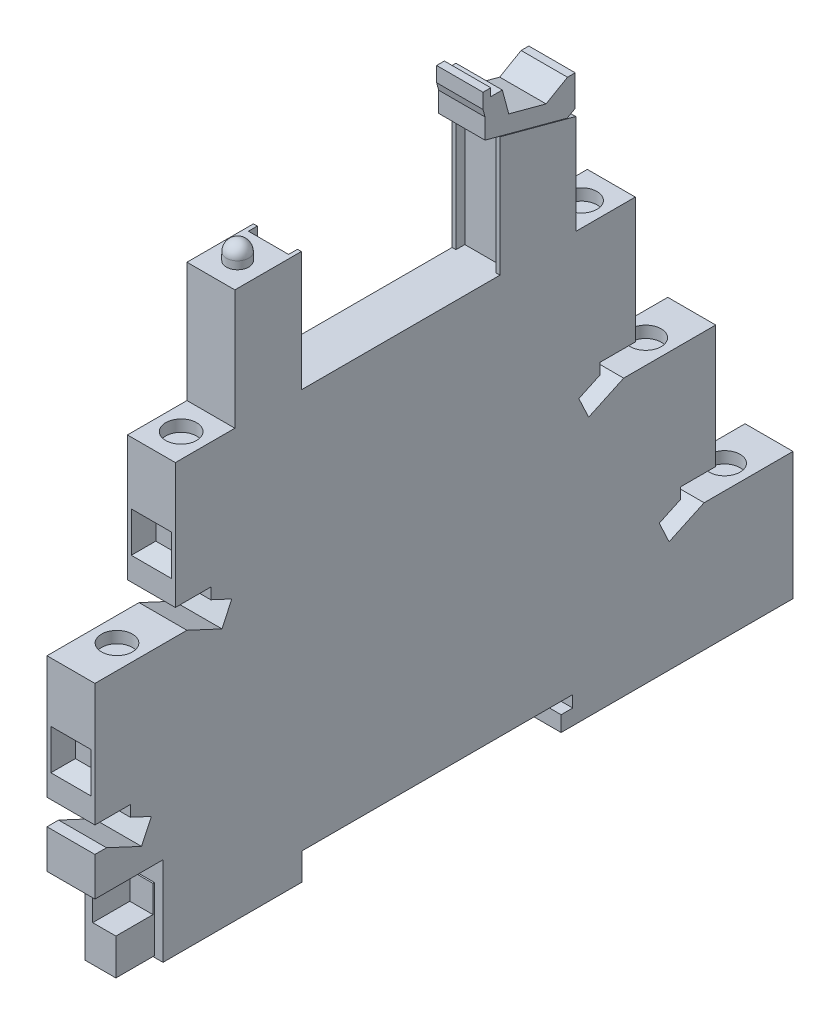
SolidWorks part; units mm, degrees
material "PVC Rigid"
ref_plane "Piano frontale" through (0, 0, 0) normal (0, 0, 1) x (1, 0, 0)
ref_plane "Piano superiore" through (0, 0, 0) normal (0, 1, 0) x (1, 0, 0)
ref_plane "Piano destro" through (0, 0, 0) normal (1, 0, 0) x (0, 0, -1)
sketch "Sketch1" plane through (0, 0, 0) normal (1, 0, 0) x (0, 0, -1)
  line L0 (0, 0) -> (0, 3.5)
  line L1 (0, 3.5) -> (35, 3.5)
  line L2 (35, 3.5) -> (35, 2)
  line L3 (35, 2) -> (33.5, 2)
  line L4 (33.5, 2) -> (33.5, 0)
  line L5 (33.5, 0) -> (63.5, 0)
  line L6 (63.5, 0) -> (63.5, 16.5)
  line L7 (63.5, 16.5) -> (52, 16.5)
  line L8 (52, 16.5) -> (47.4685, 14.3869)
  line L9 (47.4685, 14.3869) -> (46.2006, 17.1058)
  line L10 (46.2006, 17.1058) -> (48.9195, 18.3737)
  line L11 (48.9195, 18.3737) -> (48.9195, 19.8)
  line L12 (48.9195, 19.8) -> (53.5, 19.8)
  line L13 (53.5, 35.6631) -> (53.5, 19.8)
  line L14 (38.5138, 38.9631) -> (43.0943, 38.9631)
  line L15 (41.5943, 35.6631) -> (37.0627, 33.55)
  line L16 (43.0943, 55.2) -> (43.0943, 38.9631)
  line L17 (38.5138, 37.5368) -> (38.5138, 38.9631)
  line L18 (35.7949, 36.2689) -> (38.5138, 37.5368)
  line L19 (53.5, 35.6631) -> (41.5943, 35.6631)
  line L20 (37.0627, 33.55) -> (35.7949, 36.2689)
  line L21 (43.0943, 55.2) -> (35.3943, 55.2)
  line L22 (35.3943, 55.2) -> (35.3943, 68.0741)
  line L24 (25.5943, 70.7) -> (25.5943, 55.2)
  line L25 (25.5943, 55.2) -> (-0.1057, 55.2)
  line L26 (-0.1057, 55.2) -> (-0.1057, 70.7)
  line L27 (-0.1057, 70.7) -> (-8.7057, 70.7)
  line L28 (-8.7057, 70.7) -> (-8.7057, 55.2)
  line L29 (-8.7057, 55.2) -> (-16.4057, 55.2)
  line L30 (-16.4057, 55.2) -> (-16.4057, 38.9631)
  line L31 (-26.8114, 16.5) -> (-25.3114, 16.5)
  line L32 (13.3443, 46.9131) -> (13.3443, 20.627) construction
  line L33 (-22.231, 19.8) -> (-26.8114, 19.8)
  line L34 (-22.231, 18.3737) -> (-22.231, 19.8)
  line L35 (-19.512, 17.1058) -> (-22.231, 18.3737)
  line L36 (-20.7799, 14.3869) -> (-19.512, 17.1058)
  line L37 (-25.3114, 16.5) -> (-20.7799, 14.3869)
  line L38 (-26.8114, 35.6631) -> (-26.8114, 19.8)
  line L39 (-26.8114, 35.6631) -> (-14.9057, 35.6631)
  line L40 (-10.3742, 33.55) -> (-9.1063, 36.2689)
  line L41 (-9.1063, 36.2689) -> (-11.8252, 37.5368)
  line L42 (-11.8252, 37.5368) -> (-11.8252, 38.9631)
  line L43 (-14.9057, 35.6631) -> (-10.3742, 33.55)
  line L44 (-11.8252, 38.9631) -> (-16.4057, 38.9631)
  line L45 (-26.8114, 16.5) -> (-26.8114, 11.5)
  line L46 (0, 0) -> (-18, 0)
  line L47 (-18, 0) -> (-18, 11.5)
  line L48 (-18, 11.5) -> (-26.8114, 11.5)
  line L49 (25.5943, 70.7) -> (35.3943, 68.0741)
  dimension "D1" = 3.5
  dimension "D2" = 35
  dimension "D3" = 1.5
  dimension "D4" = 1.5
  dimension "D5" = 30
  dimension "D6" = 16.5
  dimension "D7" = 11.5
  dimension "D8" = 5
  dimension "D9" = 25
  dimension "D10" = 3
  dimension "D11" = 3
  dimension "D12" = 3.3
  dimension "D13" = 10
  dimension "D14" = 7.7
  dimension "D17" = 25.7
  dimension "D18" = 8.6
  dimension "D19" = 7.7
  dimension "D20" = 5
  dimension "D21" = 18
  dimension "D22" = 19.1631
  dimension "D23" = 51.7
  dimension "D24" = 55.2
extrude "Boss-Extrude1" add sketch "Sketch1" along normal blind 6.2 contours L25 L26 L27 L28 L29 L30 L44 L42 L41 L40 L43 L39 L38 L33 L34 L35 L36 L37 L31 L45 L48 L47 L46 L0 L1 L2 L3 L4 L5 L6 L7 L8 L9 L10 L11 L12 L13 L19 L15 L20 L18 L17 L14 L16 L21 L22 L49 L24
sketch "Sketch2" plane through (0, 70.7, 0) normal (0, 1, 0) x (1, 0, 0)
  line L0 (0, -0.1057) -> (0, -8.7057) construction
  line L1 (0.5, -1.2557) -> (5.7, -1.2557)
  line L2 (0.5, -1.2557) -> (0.5, 26.7443)
  line L3 (0.5, 26.7443) -> (5.7, 26.7443)
  line L4 (5.7, -1.2557) -> (5.7, 26.7443)
  line L5 (6.2, 25.5943) -> (6.2, -0.1057) construction
  line L6 (6.2, -0.1057) -> (0, -0.1057) construction
  dimension "D1" = 28
  dimension "D2" = 5.2
  dimension "D3" = 0.5
  dimension "D4" = 0.5
  dimension "D5" = 1.15
extrude "Cut-Extrude1" cut sketch "Sketch2" against normal up to vertex (15.5 mm away) up to point (0, 55.2, 0.1057)
sketch "Sketch3" plane through (0, 70.7, 0) normal (0, 1, 0) x (1, 0, 0)
  line L0 (0.5, -1.2557) -> (5.7, -1.2557) construction
  line L1 (6.2, -8.7057) -> (0, -8.7057) construction
  circle A0 centre (3.1, -5.2557) radius 1.45
  dimension "D1" = 2.9
  dimension "D3" = 3.45
  dimension "D2" = 4
extrude "Boss-Extrude2" add sketch "Sketch3" along normal blind 1 contours A0
dome "Dome1" faces to dome 1 distance 1.45 reverse direction no elliptical dome no face at (3.1, 71.7, 6.7057) parameters "D1"=1.45
sketch "Sketch4" plane through (0, 0, 18) normal (0, 0, 1) x (1, 0, 0)
  line L2 (1.1, 0.2) -> (1.1, 8.4)
  line L3 (1.1, 8.4) -> (5.1, 8.4)
  line L4 (5.1, 0.2) -> (5.1, 8.4)
  line L5 (6.2, 0) -> (6.2, 11.5) construction
  line L6 (1.1, 0.2) -> (5.1, 0.2)
  line L7 (6.2, 0) -> (0, 0) construction
  dimension "D1" = 8.2
  dimension "D2" = 8.4
  dimension "D3" = 1.1
extrude "Boss-Extrude3" add sketch "Sketch4" along normal blind 5
sketch "Sketch5" plane through (0, 0, 23) normal (0, 0, 1) x (1, 0, 0)
  line L1 (5.1, 8.4) -> (2.1, 8.4)
  line L2 (5.1, 8.4) -> (5.1, 4.9)
  line L3 (5.1, 4.9) -> (2.1, 4.9)
  line L4 (2.1, 8.4) -> (2.1, 4.9)
  dimension "D1" = 3.5
  dimension "D2" = 3
extrude "Cut-Extrude2" cut sketch "Sketch5" against normal blind 4.8
sketch "Sketch6" plane through (0, 0, 0) normal (0, 0, -1) x (-1, 0, 0)
  line L0 (-6.2, 0) -> (0, 0) construction
  line L1 (-5.1, 0) -> (-1.1, 0)
  line L2 (-5.1, 0) -> (-5.1, 2)
  line L3 (-5.1, 2) -> (-1.1, 2)
  line L4 (-1.1, 0) -> (-1.1, 2)
  line L5 (-6.2, 0) -> (-6.2, 3.5) construction
  dimension "D1" = 2
  dimension "D2" = 4
  dimension "D3" = 1.1
extrude "Boss-Extrude4" add sketch "Sketch6" along normal blind 1.5 draft 15
ref_plane "Plane1" through (3.1, 0, 0) normal (1, 0, 0) x (0, 0, -1)
sketch "Sketch7" plane through (3.1, 0, 0) normal (1, 0, 0) x (0, 0, -1)
  line L0 (34.3805, 68.3457) -> (23.7553, 71.1928)
  line L1 (25.5943, 70.7) -> (35.3943, 68.0741) construction
  line L2 (23.7553, 71.1928) -> (23.7553, 73.7928)
  line L3 (23.7553, 73.7928) -> (23.4965, 74.7587)
  line L4 (23.4965, 74.7587) -> (23.4965, 76.6928)
  line L5 (23.4965, 76.6928) -> (24.4965, 76.6928)
  line L6 (24.4965, 76.6928) -> (24.4965, 75.6928)
  line L7 (24.4965, 75.6928) -> (25.9965, 75.6928)
  line L8 (25.9965, 75.6928) -> (26.8247, 72.6018)
  line L9 (26.8247, 72.6018) -> (31.6543, 71.3077)
  line L10 (31.6543, 71.3077) -> (34.4256, 72.9077)
  line L11 (34.4256, 72.9077) -> (35.4256, 72.9077)
  line L12 (35.4256, 72.9077) -> (35.4256, 68.9077)
  line L13 (35.4256, 68.9077) -> (34.3805, 68.3457)
  dimension "D1" = 11
  dimension "D2" = 2.6
  dimension "D3" = 1
  dimension "D4" = 15
  dimension "D5" = 1
  dimension "D6" = 1
  dimension "D7" = 5.5
  dimension "D8" = 1
  dimension "D9" = 1.5
  dimension "D10" = 3.2
  dimension "D11" = 75
  dimension "D12" = 5
  dimension "D13" = 3.2
  dimension "D14" = 45
  dimension "D15" = 1
  dimension "D16" = 4
extrude "Boss-Extrude5" add sketch "Sketch7" along normal blind 3 and the other way blind 3
sketch "Sketch8" plane through (0, 55.2, 0) normal (0, 1, 0) x (1, 0, 0)
  line L0 (3.1, -42.181) -> (3.1, 42.181) construction
  circle A0 centre (3.1, 39.2443) radius 2
  circle A1 centre (3.1, -12.5557) radius 2
  dimension "D1" = 4
  dimension "D2" = 4
extrude "Cut-Extrude3" cut sketch "Sketch8" against normal blind 1.5
sketch "Sketch9" plane through (0, 35.6631, 0) normal (0, 1, 0) x (1, 0, 0)
  circle A0 centre (3.1, 47.5471) radius 2
  circle A1 centre (3.1, -20.8586) radius 2
  dimension "D1" = 4
  dimension "D2" = 4
extrude "Cut-Extrude4" cut sketch "Sketch9" against normal blind 1.5
sketch "Sketch10" plane through (0, 16.5, 0) normal (0, 1, 0) x (1, 0, 0)
  circle A0 centre (3.1, 57.75) radius 2
  dimension "D1" = 4
extrude "Cut-Extrude5" cut sketch "Sketch10" against normal blind 1.5
sketch "Sketch11" plane through (0, 0, -63.5) normal (0, 0, -1) x (-1, 0, 0)
  line L0 (-6.2, 0) -> (-6.2, 16.5) construction
  line L1 (-5.7, 3) -> (-0.5, 3)
  line L2 (-5.7, 3) -> (-5.7, 8.2)
  line L3 (-5.7, 8.2) -> (-0.5, 8.2)
  line L4 (-0.5, 3) -> (-0.5, 8.2)
  line L5 (-6.2, 0) -> (0, 0) construction
  dimension "D1" = 5.2
  dimension "D2" = 5.2
  dimension "D3" = 0.5
  dimension "D4" = 3
extrude "Cut-Extrude6" cut sketch "Sketch11" against normal blind 2.5 draft 15
sketch "Sketch12" plane through (0, 0, -53.5) normal (0, 0, -1) x (-1, 0, 0)
  line L0 (-6.2, 35.6631) -> (-6.2, 19.8) construction
  line L1 (-5.7, 22.8) -> (-0.5, 22.8)
  line L2 (-5.7, 22.8) -> (-5.7, 28)
  line L3 (-5.7, 28) -> (-0.5, 28)
  line L4 (-0.5, 22.8) -> (-0.5, 28)
  line L5 (-6.2, 19.8) -> (0, 19.8) construction
  dimension "D1" = 5.2
  dimension "D2" = 5.2
  dimension "D3" = 0.5
  dimension "D4" = 3
extrude "Cut-Extrude7" cut sketch "Sketch12" against normal blind 2.5 draft 15
sketch "Sketch13" plane through (0, 0, -43.0943) normal (0, 0, -1) x (-1, 0, 0)
  line L0 (-6.2, 55.2) -> (-6.2, 38.9631) construction
  line L1 (-5.7, 41.9631) -> (-0.5, 41.9631)
  line L2 (-5.7, 41.9631) -> (-5.7, 47.1631)
  line L3 (-5.7, 47.1631) -> (-0.5, 47.1631)
  line L4 (-0.5, 41.9631) -> (-0.5, 47.1631)
  line L5 (-6.2, 38.9631) -> (0, 38.9631) construction
  dimension "D1" = 5.2
  dimension "D2" = 0.5
  dimension "D3" = 3
extrude "Cut-Extrude8" cut sketch "Sketch13" against normal blind 2.5 draft 15
sketch "Sketch14" plane through (0, 0, 26.8114) normal (0, 0, 1) x (1, 0, 0)
  line L0 (0, 35.6631) -> (0, 19.8) construction
  line L1 (0.5, 22.8) -> (5.7, 22.8)
  line L2 (0.5, 22.8) -> (0.5, 28)
  line L3 (0.5, 28) -> (5.7, 28)
  line L4 (5.7, 22.8) -> (5.7, 28)
  line L5 (6.2, 19.8) -> (0, 19.8) construction
  dimension "D1" = 5.2
  dimension "D2" = 0.5
  dimension "D3" = 3
extrude "Cut-Extrude9" cut sketch "Sketch14" against normal blind 2.5 draft 15
sketch "Sketch15" plane through (0, 0, 16.4057) normal (0, 0, 1) x (1, 0, 0)
  line L0 (0, 55.2) -> (0, 38.9631) construction
  line L1 (0.5, 41.9631) -> (5.7, 41.9631)
  line L2 (0.5, 41.9631) -> (0.5, 47.1631)
  line L3 (0.5, 47.1631) -> (5.7, 47.1631)
  line L4 (5.7, 41.9631) -> (5.7, 47.1631)
  line L5 (6.2, 38.9631) -> (0, 38.9631) construction
  dimension "D1" = 5.2
  dimension "D2" = 0.5
  dimension "D3" = 3
extrude "Cut-Extrude10" cut sketch "Sketch15" against normal blind 2.5 draft 15
